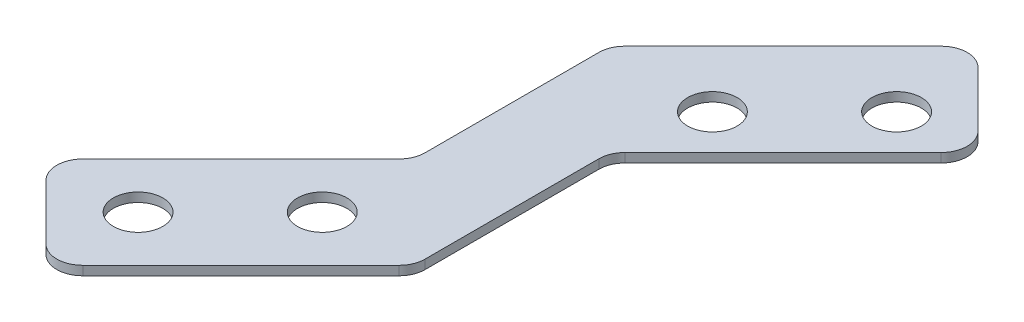
SolidWorks part; units mm, degrees
material "1060 Alloy"
ref_plane "Front Plane" through (0, 0, 0) normal (0, 0, 1) x (1, 0, 0)
ref_plane "Top Plane" through (0, 0, 0) normal (0, 1, 0) x (1, 0, 0)
ref_plane "Right Plane" through (0, 0, 0) normal (1, 0, 0) x (0, 0, -1)
sketch "Sketch1" plane through (0, 0, 0) normal (0, 1, 0) x (1, 0, 0)
  line L8 (0, 0) -> (0, 15)
  line L9 (0, 15) -> (14.1421, 29.1421)
  line L10 (14.1421, 29.1421) -> (7.0711, 36.2132)
  line L11 (7.0711, 36.2132) -> (-7.0711, 22.0711)
  line L12 (-7.0711, 22.0711) -> (-7.0711, 7.0711)
  line L13 (-7.0711, 7.0711) -> (-21.2132, -7.0711)
  line L15 (-14.1421, -14.1421) -> (0, 0)
  line L16 (-14.1421, -14.1421) -> (-21.2132, -7.0711)
  line L17 (-7.0711, 22.0711) -> (0, 15) construction
  point P6 (0, 0)
  dimension "D1" = 15
  dimension "D2" = 135
  dimension "D3" = 135
  dimension "D4" = 10
  dimension "D5" = 10
  dimension "D6" = 20
  dimension "D7" = 20
base flange "Base-Flange2" sketch "Sketch1" thickness 0.7 reverse thickness direction no parameters "D1"=1
hole_wizard "#6 Clearance Hole1" positions "Sketch10" profile "Sketch11" hole size "#6" standard "ANSI Inch" end condition through all
sketch "Sketch10" plane through (0, 0, 0) normal (0, 1, 0) x (1, 0, 0)
  line L0 (-14.1398, -7.0734) -> (-7.0688, -0.0023) construction
  line L2 (1.2374, 21.6539) -> (8.3085, 28.7249) construction
  line L4 (-14.1421, -14.1421) -> (0, 0) construction
  line L5 (0, 15) -> (14.1421, 29.1421) construction
  line L6 (-21.2132, -7.0711) -> (-14.1421, -14.1421) construction
  line L7 (14.1421, 29.1421) -> (7.0711, 36.2132) construction
  point P0 (-14.1398, -7.0734)
  point P2 (-7.0688, -0.0023)
  point P4 (1.2374, 21.6539)
  point P6 (8.3085, 28.7249)
  dimension "D1" = 5
  dimension "D2" = 10
  dimension "D3" = 4.42
  dimension "D4" = 10
  dimension "D5" = 4.9967
  dimension "D6" = 3.83
sketch "Sketch11" plane through (-14.1398, 0, 7.0734) normal (1, 0, 0) x (0, 0, 1)
  line L0 (0, 0) -> (0, 0.7)
  line L1 (0, 0.7) -> (1.8986, 0.7)
  line L2 (1.8986, 0.7) -> (1.8986, 0)
  line L5 (1.8986, 0) -> (0, 0)
  line L11 (0, -6.35) -> (0, 107.95) construction
  dimension "Thru Hole Dia." = 3.7973
  dimension "Thru Hole Depth" = 0.7
fillet "Fillet1" radius 2 8 edges at (7.0711, -0.35, -36.2132) (14.1421, -0.35, -29.1421) (-7.0711, -0.35, -7.0711) (0, -0.35, -15) (-7.0711, -0.35, -22.0711) (0, -0.35, 0) (-21.2132, -0.35, 7.0711) (-14.1421, -0.35, 14.1421)
sketch "Bend-Lines3" [suppressed] plane through (0, 0, 0) normal (0, 1, 0) x (1, 0, 0)
sketch "Bounding-Box3" [suppressed] plane through (0, 0, 0) normal (0, 1, 0) x (1, 0, 0)
sheet metal parameters "Sheet-Metal2" thickness 0.7 parameters "D1"=1
flat pattern "Flat-Pattern2" [suppressed]
sketch "Bend-Lines4" plane through (0, 0, 0) normal (0, 1, 0) x (1, 0, 0)
sketch3d "Bounding-Box4" [suppressed]
  line L0 (18.9739, 32.9272, 0) -> (-12.0539, -20.9183, 0) construction
  line L1 (4.9829, 40.9894, 0) -> (-26.045, -12.8561, 0) construction
  line L2 (18.9739, 32.9272, 0) -> (4.9829, 40.9894, 0) construction
  line L3 (-12.0539, -20.9183, 0) -> (-26.045, -12.8561, 0) construction
sheet metal parameters "Sheet-Metal3" thickness 0.7 parameters "D1"=1
flat pattern "Flat-Pattern2"
sketch "Bend-Lines4" plane through (0, 0, 0) normal (0, 1, 0) x (1, 0, 0)
sketch3d "Bounding-Box4" [suppressed]
  line L0 (14.8402, 31.9416, 0) -> (-7.9154, -16.4517, 0) construction
  line L1 (0.8444, 38.5228, 0) -> (-21.9112, -9.8706, 0) construction
  line L2 (14.8402, 31.9416, 0) -> (0.8444, 38.5228, 0) construction
  line L3 (-7.9154, -16.4517, 0) -> (-21.9112, -9.8706, 0) construction
equation "\"D2@Sketch1\"=90+45"
equation "\"D3@Sketch1\"=\"D2@Sketch1\""
equation "\"D5@Sketch1\"=\"D4@Sketch1\""
equation "\"D7@Sketch1\"=\"D6@Sketch1\""
